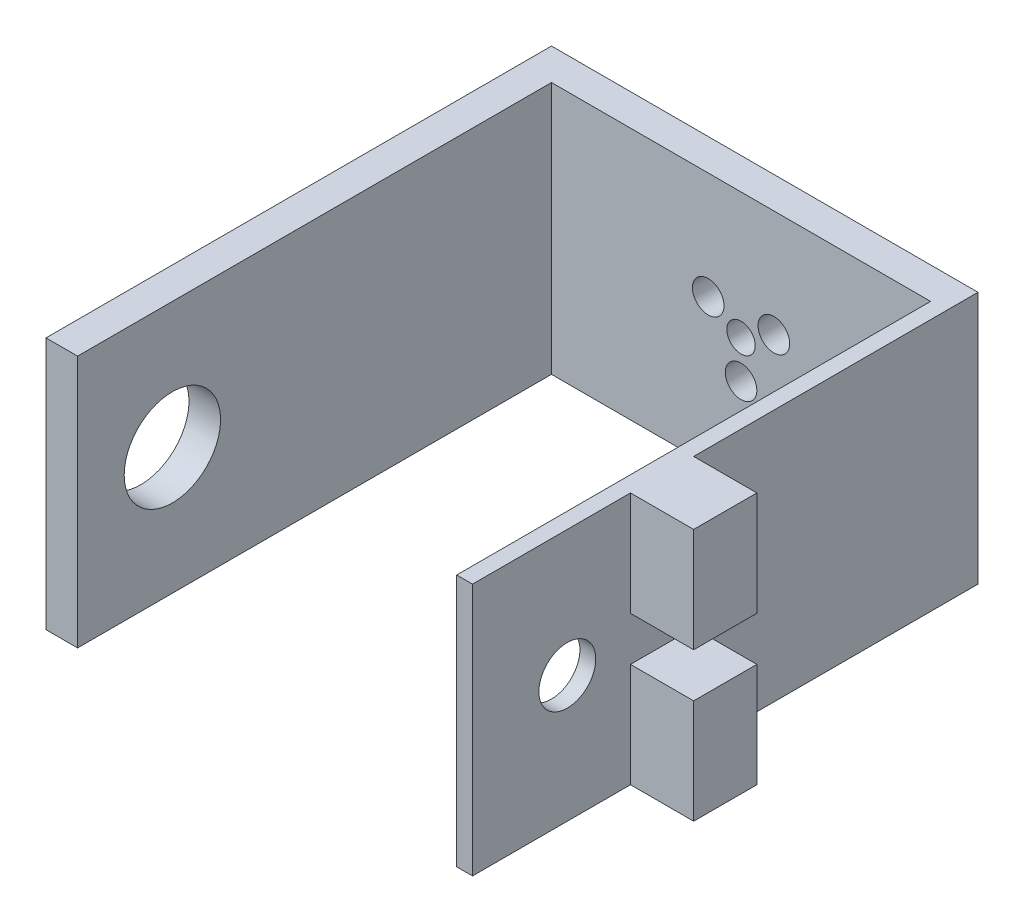
SolidWorks part; units mm, degrees
ref_plane "Front Plane" through (0, 0, 0) normal (0, 0, 1) x (1, 0, 0)
ref_plane "Top Plane" through (0, 0, 0) normal (0, 1, 0) x (1, 0, 0)
ref_plane "Right Plane" through (0, 0, 0) normal (1, 0, 0) x (0, 0, -1)
sketch "Sketch1" plane through (0, 0, 0) normal (0, 1, 0) x (1, 0, 0)
  line L0 (-991.4904, 0) -> (48583.0319, 0) construction
  line L1 (0, -991.4904) -> (0, 48583.0319) construction
  line L2 (-35, -42.2693) -> (-30, -42.2693)
  line L3 (-30, -42.2693) -> (-30, 32.7307)
  line L4 (-30, 32.7307) -> (30, 32.7307)
  line L5 (30, 32.7307) -> (30, -42.2693)
  line L6 (30, -42.2693) -> (32.5, -42.2693)
  line L7 (32.5, -42.2693) -> (32.5, 37.7307)
  line L8 (32.5, 37.7307) -> (-35, 37.7307)
  line L9 (-35, -42.2693) -> (-35, 37.7307)
  dimension "D1" = 2.5
  dimension "D2" = 5
  dimension "D3" = 80
  dimension "D4" = 30
  dimension "D5" = 5
extrude "Boss-Extrude1" add sketch "Sketch1" along normal blind 40
sketch "Sketch2" plane through (0, 0, -37.7307) normal (0, 0, -1) x (-1, 0, 0)
  line L0 (-1000, 20.0389) -> (49000, 20.0389) construction
  line L1 (0.0024, -980) -> (0.0024, 49020) construction
  line L2 (868.3667, -481.3114) -> (-42432.9035, 24518.6886) construction
  line L3 (-868.3977, -481.3321) -> (42432.8725, 24518.6679) construction
  line L4 (-32.5, 0) -> (35, 0)
  line L5 (35, 0) -> (35, 40)
  line L6 (35, 40) -> (-32.5, 40)
  line L7 (-32.5, 40) -> (-32.5, 0)
  line L8 (-32.5, 0) -> (35, 0)
  line L9 (35, 0) -> (35, 40)
  line L10 (35, 40) -> (-32.5, 40)
  line L11 (-32.5, 40) -> (-32.5, 0)
  circle A0 centre (0.0024, 20.0389) radius 10
  circle A1 centre (0.0024, 14.0389) radius 2.5
  circle A2 centre (-5.1937, 23.0389) radius 2.5
  circle A3 centre (5.1986, 23.0389) radius 2.5
  circle A4 centre (0.0024, 20.0389) radius 2.25
  point P6 (1.25, 40)
  dimension "D3" = 20
  dimension "D5" = 5
  dimension "D8" = 120
  dimension "D10" = 4.5
  dimension "D2" = 20
  dimension "D4" = 6
  dimension "D6" = 6
  dimension "D7" = 6
  dimension "D9" = 120
  dimension "D1" = 0
extrude "Cut-Extrude1" cut sketch "Sketch2" against normal through all contours A3 | A1 | A2 region at (-0.0024, 14.0389, -37.7307) region at (5.1937, 23.0389, -37.7307) region at (-5.1986, 23.0389, -37.7307)
sketch "Sketch3" plane through (-35, 0, 0) normal (-1, 0, 0) x (0, 0, 1)
  line L4 (-37.7307, 0) -> (42.2693, 0)
  line L5 (42.2693, 0) -> (42.2693, 40)
  line L6 (42.2693, 40) -> (-37.7307, 40)
  line L7 (-37.7307, 40) -> (-37.7307, 0)
  line L8 (-37.7307, 0) -> (42.2693, 0)
  line L9 (42.2693, 0) -> (42.2693, 40)
  line L10 (42.2693, 40) -> (-37.7307, 40)
  line L11 (-37.7307, 40) -> (-37.7307, 0)
  circle A0 centre (27.2693, 20) radius 7.625
  dimension "D3" = 15.25
  dimension "D2" = 65
  dimension "D1" = 0
extrude "Cut-Extrude2" cut sketch "Sketch3" against normal up to next contours A0 region at (-35, 20, 27.2693)
sketch "Sketch4" plane through (32.5, 0, 0) normal (1, 0, 0) x (0, 0, -1)
  line L0 (-17.2693, 23.5) -> (-7.2693, 23.5)
  line L1 (-7.2693, 0) -> (-17.2693, 0)
  line L2 (-7.2693, 0) -> (-7.2693, 40)
  line L3 (-7.2693, 40) -> (-17.2693, 40)
  line L4 (-42.2693, 0) -> (37.7307, 0)
  line L5 (37.7307, 0) -> (37.7307, 40)
  line L6 (37.7307, 40) -> (-42.2693, 40)
  line L7 (-42.2693, 40) -> (-42.2693, 0)
  line L8 (-42.2693, 0) -> (37.7307, 0)
  line L9 (37.7307, 0) -> (37.7307, 40)
  line L10 (37.7307, 40) -> (-42.2693, 40)
  line L11 (-42.2693, 40) -> (-42.2693, 0)
  line L12 (-17.2693, 0) -> (-17.2693, 40)
  line L13 (-7.2693, 0) -> (-17.2693, 40) construction
  line L14 (-7.2693, 40) -> (-17.2693, 0) construction
  line L15 (-17.2693, 16.5) -> (-7.2693, 16.5)
  line L16 (-17.2693, 20) -> (-7.2693, 20) construction
  circle A0 centre (-27.2693, 20) radius 7.625 construction
  circle A1 centre (-27.2693, 20) radius 7.625 construction
  circle A2 centre (-27.2693, 20) radius 4.5
  point P7 (-12.2693, 20)
  line M6 (-42.2693, 0) -> (37.7307, 0)
  line M8 (37.7307, 40) -> (-42.2693, 40)
  dimension "D3" = 9
  dimension "D2" = 10
  dimension "D4" = 10
  dimension "D5" = 7
  dimension "D1" = 0
extrude "Cut-Extrude4" cut sketch "Sketch4" against normal blind 10 contours A2 region at (32.5, 20, 27.2693)
extrude "Boss-Extrude2" add sketch "Sketch4<4>" along normal blind 10 contours L15 L12 L2 M6 | L12 L0 L2 M8 region at (32.5, 31.75, 12.2693) region at (32.5, 8.25, 12.2693)
sketch "Sketch4<4>" plane through (32.5, 0, 0) normal (1, 0, 0) x (0, 0, -1) same geometry as "Sketch4"
extrude "Cut-Extrude5" cut sketch "Sketch2<3>" against normal up to next contours A4 region at (-0.0024, 20.0389, -37.7307)
sketch "Sketch2<3>" plane through (0, 0, -37.7307) normal (0, 0, -1) x (-1, 0, 0) same geometry as "Sketch2"
